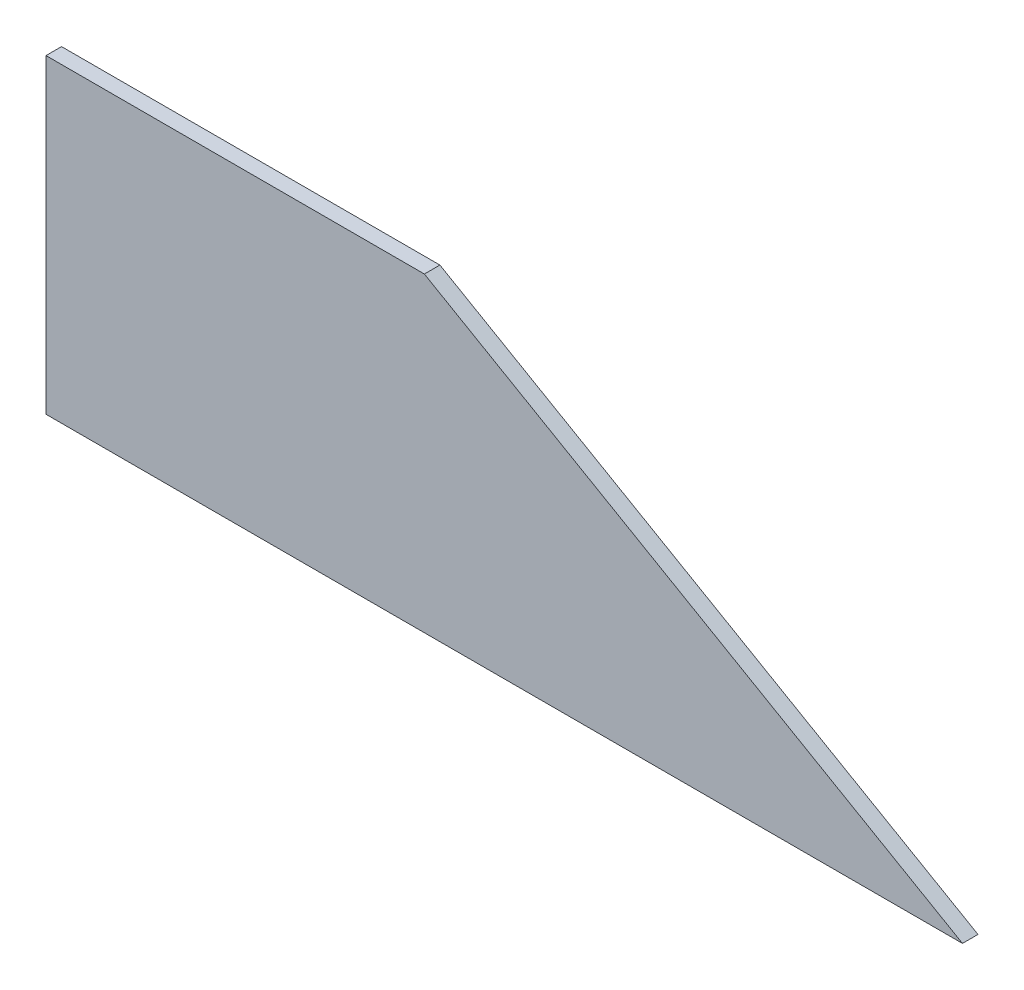
SolidWorks part; units mm, degrees
ref_plane "Front Plane" through (0, 0, 0) normal (0, 0, 1) x (1, 0, 0)
ref_plane "Top Plane" through (0, 0, 0) normal (0, 1, 0) x (1, 0, 0)
ref_plane "Right Plane" through (0, 0, 0) normal (1, 0, 0) x (0, 0, -1)
sketch "Sketch1" plane through (0, 0, 0) normal (0, 0, 1) x (1, 0, 0)
  line L0 (77.3398, 63.5) -> (187.325, 0)
  line L1 (0, 0) -> (77.3398, 0)
  line L2 (0, 0) -> (0, 63.5)
  line L3 (0, 63.5) -> (77.3398, 63.5)
  line L5 (187.325, 0) -> (77.3398, 0)
  dimension "D1" = 187.325
  dimension "D2" = 30
  dimension "D3" = 127
extrude "Boss-Extrude1" add sketch "Sketch1" along normal blind 3.175
sketch "Sketch2" [suppressed] plane through (0, 0, 3.175) normal (0, 0, 1) x (1, 0, 0)
  line L0 (0, 0) -> (177.8, 0) construction
  line L1 (6.35, 0) -> (133.35, 0)
  line L2 (6.35, 0) -> (6.35, 19.05)
  line L3 (6.35, 19.05) -> (133.35, 19.05)
  line L4 (133.35, 0) -> (133.35, 19.05)
  line L5 (0, 63.5) -> (0, 0) construction
  dimension "D1" = 127
  dimension "D2" = 19.05
  dimension "D3" = 6.35
extrude "Cut-Extrude1" [suppressed] cut sketch "Sketch2" against normal blind 3.175
